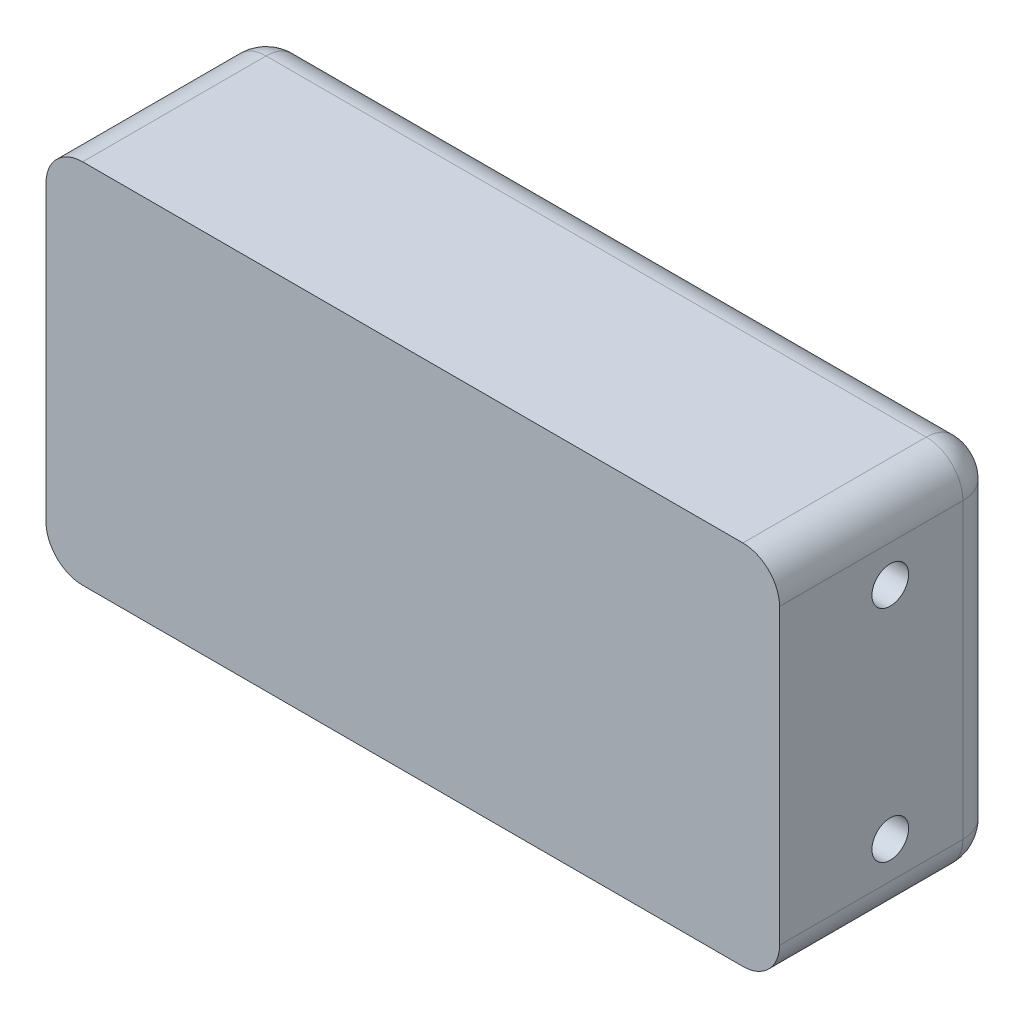
SolidWorks part; units mm, degrees
ref_plane "Front Plane" through (0, 0, 0) normal (0, 0, 1) x (1, 0, 0)
ref_plane "Top Plane" through (0, 0, 0) normal (0, 1, 0) x (1, 0, 0)
ref_plane "Right Plane" through (0, 0, 0) normal (1, 0, 0) x (0, 0, -1)
sketch "Sketch1" plane through (0, 0, 0) normal (0, 0, 1) x (1, 0, 0)
  line L1 (-50, 25) -> (50, 25)
  line L2 (-50, 25) -> (-50, -25)
  line L3 (-50, -25) -> (50, -25)
  line L4 (50, 25) -> (50, -25)
  line L5 (-50, 25) -> (50, -25) construction
  line L6 (-50, -25) -> (50, 25) construction
  point P0 (0, 0)
  dimension "D1" = 50
  dimension "D2" = 100
extrude "Boss-Extrude1" add sketch "Sketch1" along normal blind 30
sketch "Sketch2" plane through (50, 0, 0) normal (1, 0, 0) x (0, 0, -1)
  line L0 (-30, 25) -> (0, 25) construction
  circle A0 centre (-14.9035, 15) radius 2.5
  circle A1 centre (-14.9035, -15) radius 2.5
  dimension "D1" = 5
  dimension "D2" = 5
  dimension "D3" = 30
  dimension "D4" = 10
extrude "Cut-Extrude1" cut sketch "Sketch2" against normal through all
fillet "Fillet1" radius 5 4 edges at (50, 0, 0) (0, -25, 0) (-50, 0, 0) (0, 25, 0)
sketch "Sketch3" plane through (0, 0, 0) normal (0, 0, -1) x (-1, 0, 0)
  line L0 (-50, 25) -> (50, 25) construction
  line L1 (-50, -25) -> (-50, 25) construction
  line L2 (50, 25) -> (50, -25) construction
  circle A0 centre (-30, 15) radius 2.5
  circle A1 centre (30, 15) radius 2.5
  circle A2 centre (0, 15) radius 2.5
  dimension "D1" = 5
  dimension "D2" = 5
  dimension "D5" = 5
  dimension "D3" = 10
  dimension "D4" = 10
  dimension "D6" = 10
  dimension "D7" = 20
  dimension "D8" = 20
  dimension "D9" = 30
extrude "Cut-Extrude2" cut sketch "Sketch3" against normal up to surface (12.4035 mm away) up to face at (-50, 17.5, 14.9035)
fillet "Fillet2" radius 5 8 edges at (48.5355, 23.5355, 1.4645) (48.5355, -23.5355, 1.4645) (-48.5355, 23.5355, 1.4645) (-48.5355, -23.5355, 1.4645) (50, 25, 17.5) (50, -25, 17.5) (-50, 25, 17.5) (-50, -25, 17.5)
